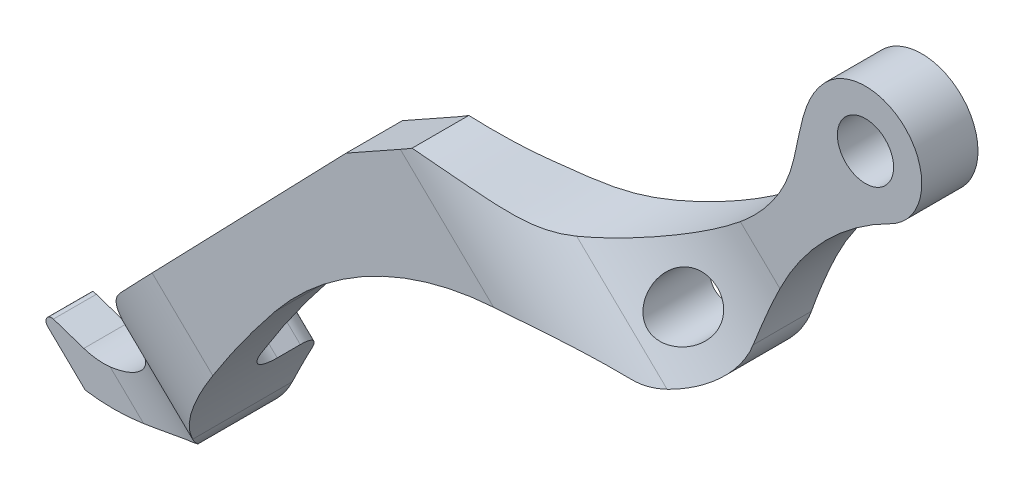
SolidWorks part; units mm, degrees
ref_plane "前基準面" through (0, 0, 0) normal (0, 0, 1) x (1, 0, 0)
ref_plane "上基準面" through (0, 0, 0) normal (0, 1, 0) x (1, 0, 0)
ref_plane "右基準面" through (0, 0, 0) normal (1, 0, 0) x (0, 0, -1)
sketch "草圖1" plane through (0, 0, 0) normal (0, 0, 1) x (1, 0, 0)
  line L0 (0, 0) -> (35.657, 18.1268) construction
  line L1 (35.657, 18.1268) -> (21.5, 0) construction
  line L2 (21.5, 0) -> (0, 0) construction
  line L3 (33.2106, 22.4874) -> (9.2127, 9.0241)
  line L4 (9.2127, -5) -> (21.5, -5)
  line L5 (25.4406, -3.0776) -> (39.5976, 15.0492)
  line L6 (9.2127, -5) -> (9.2127, -41.3862)
  line L11 (9.2127, 13.2175) -> (-51.0185, 13.2175)
  line L12 (9.2127, 13.2175) -> (9.2127, 9.0241)
  line L13 (9.2127, -41.3862) -> (-51.0185, -41.3862)
  line L14 (-51.0185, 13.2175) -> (-51.0185, -41.3862)
  circle A0 centre (0, 0) radius 2.5 construction
  circle A1 centre (21.5, 0) radius 2.5
  circle A2 centre (35.657, 18.1268) radius 2.5
  arc A4 (39.5976, 15.0492) -> (33.2106, 22.4874) centre (35.657, 18.1268) ccw
  arc A5 (21.5, -5) -> (25.4406, -3.0776) centre (21.5, 0) ccw
  circle A7 centre (21.5, 0) radius 5 construction
  circle A8 centre (35.657, 18.1268) radius 5 construction
  dimension "D4" = 5
  dimension "D1" = 40
  dimension "D2" = 23
  dimension "D3" = 21.5
  dimension "D5" = 2.5
extrude "填料-伸長1" add sketch "草圖1" along normal mid plane 12
sketch "草圖2" plane through (0, 0, 6) normal (0, 0, 1) x (1, 0, 0)
  line L0 (33.2106, 22.4874) -> (9.2127, 9.0241) construction
  line L5 (-3.5047, 1.8894) -> (-24.4991, -19.8371)
  line L7 (2.3035, 5.1479) -> (-3.5047, 1.8894)
  line L8 (-27.3354, -29.1023) -> (-32.5461, -32.1174) construction
  line L10 (-34.0049, -31.9849) -> (-38.8067, -30.3712)
  line L12 (-38.8067, -30.3712) -> (-33.8756, -35.1362)
  line L16 (-26.9401, -27.7851) -> (-26.0939, -22.9682)
  arc A0 (-26.9401, -27.7851) -> (-34.0049, -31.9849) centre (-32.2784, -26.8472) cw
  arc A1 (21.5, -5) -> (25.4406, -3.0776) centre (21.5, 0) ccw construction
  arc A2 (39.5976, 15.0492) -> (33.2106, 22.4874) centre (35.657, 18.1268) ccw construction
  arc A3 (-26.0939, -22.9682) -> (-24.4991, -19.8371) centre (-20.1844, -24.0064) cw
  arc A4 (19.9292, -4.7469) -> (26.3839, -1.0712) centre (21.5, 0) ccw
  arc A5 (37.8795, 13.6479) -> (32.0722, 21.6124) centre (35.657, 18.1268) ccw
  arc A6 (37.8795, 13.6479) -> (26.3839, -1.0712) centre (47.4798, -5.6985) ccw
  arc A7 (19.9292, -4.7469) -> (-9.8512, -13.4921) centre (11.3597, -30.6434) ccw
  arc A14 (-9.8512, -13.4921) -> (-20.2786, -30.0889) centre (54.3335, -65.3923) ccw
  arc A15 (-20.2786, -30.0889) -> (-23.5207, -33.4335) centre (-26.8158, -26.9957) cw
  arc A16 (-23.5207, -33.4335) -> (-33.8756, -35.1362) centre (-31.3549, -18.1277) cw
  spline S0 degree 3 poles (32.0722, 21.6124) (29.6196, 19.09) (30.5294, 9.3841) (14.4971, 0.221) (7.8953, 4.291) (2.3035, 5.1479) knots 0 0 0 0 0.241566 0.691253 1 1 1 1
  point P2 (0, 0)
  point P5 (-38.7718, -30.3829)
  point P7 (0, 0)
  point P8 (0, 0)
  point P28 (0, 0)
  point P29 (0, 0)
  point P41 (-39.3805, -29.8168)
  point P42 (-39.8751, -30.0121)
  dimension "D1" = 6
extrude "除料-伸長1" cut sketch "草圖2" against normal blind 12 flip side to cut
sketch "草圖3" plane through (-2.7565, 2.6636, 0) normal (-0.7191, 0.6949, 0) x (0, 0, 1)
  line L0 (-6.1877, -50.2346) -> (-6.0185, -32.1138)
  line L1 (-6, -1.0767) -> (-6, -31.2893) construction
  line L2 (-4.0186, -30.1324) -> (-1.9681, -30.1324)
  line L3 (1, -27.1643) -> (1, 4.2148)
  line L4 (6, -1.0767) -> (6, -31.2893) construction
  line L6 (-6, 22.1808) -> (-6, 42.8129)
  line L7 (-6, 42.8129) -> (-1, 42.8129)
  line L8 (6, 42.8129) -> (-6, 42.8129) construction
  line L9 (-1, 42.8129) -> (-1, 22.1808)
  line L11 (6, 5.3026) -> (6, 37.8285) construction
  line L12 (6, 4.2148) -> (6, -25.8852)
  line L13 (6, -34.6492) -> (6, -38.7011) construction
  line L15 (-1.1877, -45.1847) -> (-1.1877, -50.2346)
  line L17 (-1.1877, -50.2346) -> (-6.1877, -50.2346)
  arc A0 (-6.0185, -32.1138) -> (-4.0186, -30.1324) centre (-4.0186, -32.1324) cw
  arc A1 (-1, 22.1808) -> (3.0554, 11.7723) centre (14.3848, 22.1808) ccw
  arc A2 (3.0554, 11.7723) -> (6, 4.2148) centre (-5.1708, 4.2148) cw
  arc A3 (-6, 22.1808) -> (-0.6266, 8.3896) centre (14.3848, 22.1808) ccw
  arc A4 (-0.6266, 8.3896) -> (1, 4.2148) centre (-5.1708, 4.2148) cw
  arc A5 (-0.6266, 8.3896) -> (1, 4.2148) centre (-5.1708, 4.2148) cw construction
  arc A6 (-6, 22.1808) -> (-0.6266, 8.3896) centre (14.3848, 22.1808) ccw construction
  arc A7 (-1.9681, -30.1324) -> (1, -27.1643) centre (-1.9681, -27.1643) ccw
  arc A8 (-1.1877, -45.1847) -> (1.8514, -37.0245) centre (11.2873, -45.1847) cw
  arc A9 (1.8514, -37.0245) -> (6, -25.8852) centre (-11.0292, -25.8852) ccw
  point P25 (0, 0)
  point P26 (6, -28.1229)
  point P28 (-6, -30.1324)
  point P32 (3.9576, -32.9711)
  point P33 (6, -25.3014)
  point P36 (1.8514, -37.0245)
  dimension "D1" = 2
  dimension "D2" = 5
  dimension "D3" = 5
  dimension "D4" = 5
  dimension "D5" = 5
extrude "除料-伸長2" cut sketch "草圖3" against normal through all and the other way blind 10 flip side to cut
chamfer "導角1" distance 1.5 distance2 1 4 edges at (-26.517, -25.3767, -6) (-36.4058, -31.178, -6) (-25.6545, -21.5411, -6) (-29.5088, -31.5062, -6) first distance on face at (-27.2968, -29.0129, -6)
fillet "圓角1" radius 0.5 1 edges at (-38.8067, -30.3712, -3.0938)
